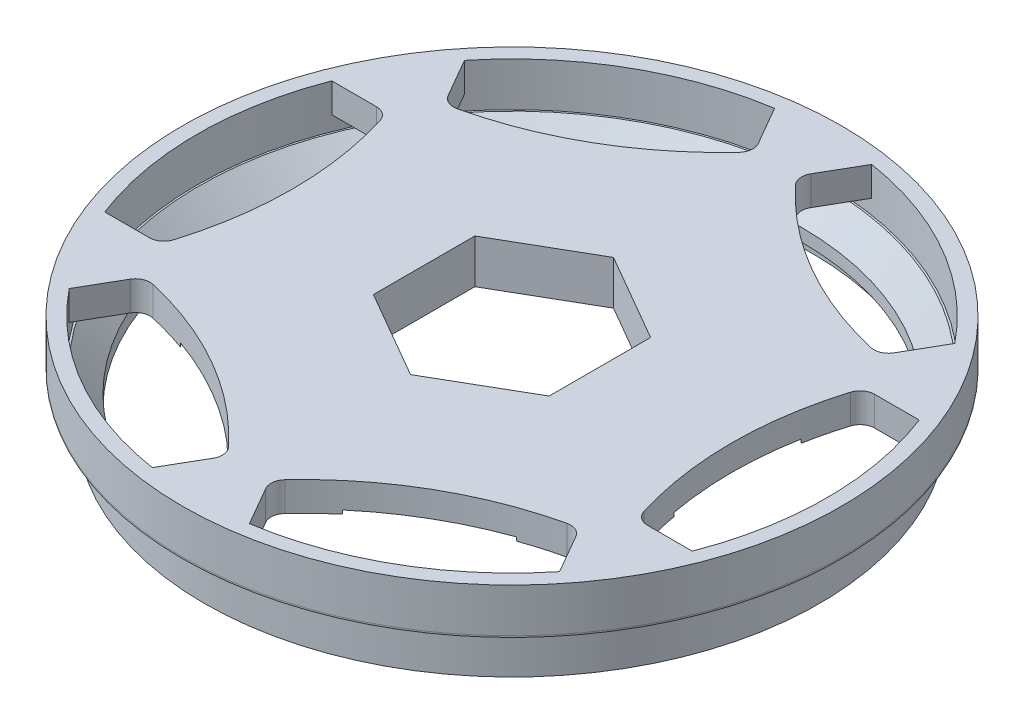
SolidWorks part; units mm, degrees
ref_plane "Ebene vorne" through (0, 0, 0) normal (0, 0, 1) x (1, 0, 0)
ref_plane "Ebene oben" through (0, 0, 0) normal (0, 1, 0) x (1, 0, 0)
ref_plane "Ebene rechts" through (0, 0, 0) normal (1, 0, 0) x (0, 0, -1)
sketch "Skizze1" plane through (0, 0, 0) normal (0, 1, 0) x (1, 0, 0)
  circle A0 centre (0, 0) radius 44
  dimension "D1" = 88
extrude "Aufsatz-Linear austragen1" add sketch "Skizze1" along normal blind 4
sketch "Skizze2" plane through (0, 4, 0) normal (0, 1, 0) x (1, 0, 0)
  line L0 (-32.5715, 15.5) -> (-71.0776, 15.5)
  line L1 (-32.5715, -15.5) -> (-71.0776, -15.5)
  line L2 (-71.0776, 15.5) -> (-71.0776, -15.5)
  circle A0 centre (-78, 0) radius 48
  circle M2 centre (0, 0) radius 44
  dimension "D1" = 78
  dimension "D2" = 96
  dimension "D3" = 31
  dimension "D4" = 15.5
extrude "Schnitt-Linear austragen2" cut sketch "Skizze2" against normal blind 10 contours L1 A0 L0 M2 region at (-36.9648, 4, 0)
sketch "Skizze4" plane through (0, 4, 0) normal (0, 1, 0) x (1, 0, 0)
  circle A0 centre (0, 0) radius 21.0071
extrude "Aufsatz-Linear austragen4" add sketch "Skizze4" against normal blind 6
pattern_circular "Kreismuster1" count 6 over 360 about axis through (0, 0, 0) along (0, 1, 0) of "Schnitt-Linear austragen2"
sketch "Skizze3" plane through (0, 0, 0) normal (0, -1, 0) x (1, 0, 0)
  line L1 (12, 6.9282) -> (0, 13.8564)
  line L2 (0, 13.8564) -> (-12, 6.9282)
  line L3 (-12, 6.9282) -> (-12, -6.9282)
  line L4 (-12, -6.9282) -> (0, -13.8564)
  line L5 (0, -13.8564) -> (12, -6.9282)
  line L6 (12, -6.9282) -> (12, 6.9282)
  circle A0 centre (0, 0) radius 12 construction
extrude "Schnitt-Linear austragen3" cut sketch "Skizze3" against normal blind 10 and the other way blind 4
fillet "Verrundung1" radius 2 12 edges at (-32.5715, 2, 15.5) (-2.8623, 2, 35.9577) (2.8623, 2, 35.9577) (29.7091, 2, 20.4577) (32.5715, 2, 15.5) (32.5715, 2, -15.5) (29.7091, 2, -20.4577) (2.8623, 2, -35.9577) (-2.8623, 2, -35.9577) (-29.7091, 2, -20.4577) (-32.5715, 2, -15.5) (-29.7091, 2, 20.4577)
sketch "Skizze5" plane through (13.4234, 0, 7.75) normal (-0.866, 0, -0.5) x (-0.5, 0, 0.866)
  line L0 (-34.0256, 0) -> (-41.1795, 0) construction
  circle A0 centre (-39, 0) radius 1.6
sketch "Skizze6" plane through (0, 0, -15.5) normal (0, 0, 1) x (1, 0, 0)
  line L0 (34.0256, 0) -> (41.1795, 0) construction
  circle A0 centre (39, 0) radius 1.6
sketch "Skizze8" plane through (0, 4, 0) normal (0, 1, 0) x (1, 0, 0)
  circle A0 centre (0, 0) radius 45
  circle A1 centre (0, 0) radius 43
extrude "Aufsatz-Linear austragen2" add sketch "Skizze8" against normal blind 6
sketch "Skizze9" plane through (0, -2, 0) normal (0, -1, 0) x (1, 0, 0)
  circle A0 centre (0, 0) radius 45
  circle A1 centre (0, 0) radius 39.5
extrude "Aufsatz-Linear austragen3" add sketch "Skizze9" along normal blind 7 separate body
chamfer "Fase1" distance 3.25 angle 45 1 edges at (0, -2, -39.5)
sketch "Skizze7" plane through (0, 0, 0) normal (0, -1, 0) x (1, 0, 0)
  circle A0 centre (0, 0) radius 32
  circle A1 centre (0, 0) radius 21.5
extrude "Schnitt-Linear austragen7" cut sketch "Skizze7" against normal blind 0.5
sketch "Skizze10" plane through (0, -9, 0) normal (0, -1, 0) x (1, 0, 0)
  circle A0 centre (0, 0) radius 42
  circle A1 centre (0, 0) radius 50
extrude "Schnitt-Linear austragen9" cut sketch "Skizze10" against normal blind 6 contours A1 | A0
sketch "Skizze11" plane through (0, -9, 0) normal (0, -1, 0) x (1, 0, 0)
  circle A0 centre (0, 0) radius 40.9
  circle A1 centre (-1.9486, 1.7726) radius 30
extrude "Schnitt-Linear austragen10" cut sketch "Skizze11" against normal blind 2
chamfer "Fase2" distance 3 angle 15 1 edges at (0, -3, -45) first distance on face at (0, -3, -42)
chamfer "Fase3" distance 2 angle 45 1 edges at (0, -2, 21.0071)
